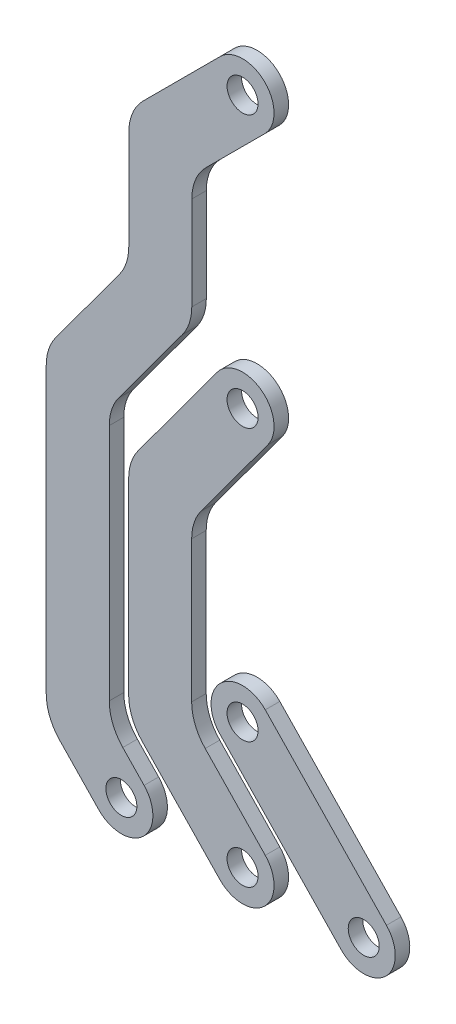
SolidWorks part; units mm, degrees
ref_plane "前视基准面" through (0, 0, 0) normal (0, 0, 1) x (1, 0, 0)
ref_plane "上视基准面" through (0, 0, 0) normal (0, 1, 0) x (1, 0, 0)
ref_plane "右视基准面" through (0, 0, 0) normal (1, 0, 0) x (0, 0, -1)
sketch "草图1"
  dimension "D1" = 26
  dimension "D2" = 0
sketch_block_instance "块1-1"
sketch_block "块1"
sketch_block_instance "块2-1"
sketch_block "块2"
sketch "草图2" plane through (0, 0, 0) normal (0, 0, 1) x (1, 0, 0)
  circle A0 centre (-5.5865, -343.2) radius 6.5
  circle A1 centre (-5.5865, -287.2) radius 6
  circle A2 centre (-5.5865, -287.2) radius 6
  circle A3 centre (-5.5865, -343.2) radius 6
  circle A4 centre (-5.5865, -343.2) radius 6
  circle A5 centre (-5.5865, -231.2) radius 6
  circle A6 centre (-5.5865, -231.2) radius 6
  circle A7 centre (-30.5865, -369.2) radius 2.5
  circle A8 centre (-30.5865, -369.2) radius 2.5
  circle A9 centre (-5.5865, -369.2) radius 2.5
  circle A10 centre (-5.5865, -369.2) radius 2.5
  circle A11 centre (19.4135, -369.2) radius 2.5
  circle A12 centre (19.4135, -369.2) radius 2.5
  circle A13 centre (-5.5865, -287.2) radius 6.5
  circle A14 centre (-5.5865, -231.2) radius 6.5
  circle A15 centre (-5.5865, -369.2) radius 6.5
  circle A16 centre (19.4135, -369.2) radius 6.5
  circle A17 centre (-30.5865, -369.2) radius 6.5
  dimension "D4" = 13
  dimension "D8" = 13
  dimension "D9" = 13
  dimension "D1" = 0
  dimension "D2" = 0
  dimension "D3" = 0
  dimension "D5" = 0
  dimension "D6" = 0
  dimension "D7" = 0
  dimension "D10" = 0.5
sketch "草图3" plane through (0, 0, 0) normal (0, 0, 1) x (1, 0, 0)
  line L26 (-5.5865, -287.2) -> (-22.5865, -310.3173)
  line L27 (-22.5865, -310.3173) -> (-22.5865, -351.52)
  line L28 (-22.5865, -351.52) -> (-5.5865, -369.2)
  line L29 (-39.5865, -298.5954) -> (-5.5865, -252.3607)
  line L30 (-39.5865, -298.5954) -> (-39.5865, -359.84)
  line L31 (-39.5865, -359.84) -> (-30.5865, -369.2)
  line L32 (-5.5865, -343.2) -> (19.4135, -369.2)
  line L33 (-10.2719, -347.7052) -> (14.7281, -373.7052)
  line L34 (-0.9011, -338.6948) -> (24.0989, -364.6948)
  line L35 (-5.5865, -252.3607) -> (-5.5865, -231.2)
  line L36 (-10.8231, -283.3492) -> (-29.0865, -308.1846)
  line L37 (-29.0865, -308.1846) -> (-29.0865, -354.138)
  line L38 (-29.0865, -354.138) -> (-10.2719, -373.7052)
  line L39 (-33.0865, -357.222) -> (-25.9011, -364.6948)
  line L40 (-33.0865, -300.7281) -> (-33.0865, -357.222)
  line L41 (-33.0865, -300.7281) -> (0.9135, -254.4934)
  line L42 (0.9135, -254.4934) -> (0.9135, -231.2)
  line L43 (-0.35, -291.0508) -> (-16.0865, -312.45)
  line L44 (-16.0865, -312.45) -> (-16.0865, -348.902)
  line L45 (-16.0865, -348.902) -> (-0.9011, -364.6948)
  line L46 (-46.0865, -362.458) -> (-35.2719, -373.7052)
  line L47 (-46.0865, -296.4627) -> (-46.0865, -362.458)
  line L48 (-46.0865, -296.4627) -> (-12.0865, -250.228)
  line L49 (-12.0865, -250.228) -> (-12.0865, -231.2)
  circle A13 centre (-5.5865, -343.2) radius 6.5
  circle A14 centre (-5.5865, -343.2) radius 6.5
  circle A15 centre (-30.5865, -369.2) radius 6.5
  circle A16 centre (-30.5865, -369.2) radius 6.5
  circle A17 centre (19.4135, -369.2) radius 6.5
  circle A18 centre (19.4135, -369.2) radius 6.5
  circle A19 centre (-5.5865, -369.2) radius 6.5
  circle A20 centre (-5.5865, -369.2) radius 6.5
  circle A21 centre (-5.5865, -231.2) radius 6.5
  circle A22 centre (-5.5865, -231.2) radius 6.5
  circle A23 centre (-5.5865, -287.2) radius 6.5
  circle A24 centre (-5.5865, -287.2) radius 6.5
  dimension "D2" = 6.5
  dimension "D3" = 6.5
  dimension "D4" = 6.5
  dimension "D5" = 6.5
  dimension "D6" = 7.64
  dimension "D7" = 4
  dimension "D9" = 4
  dimension "D10" = 143.67
  dimension "D8" = 0
  dimension "D11" = 0
  dimension "D12" = 0
  dimension "D13" = 0
  dimension "D14" = 0
  dimension "D15" = 0
sketch "草图4" plane through (0, 0, 0) normal (0, 0, 1) x (1, 0, 0)
  line L3 (-33.0865, -357.222) -> (-25.9011, -364.6948) construction
  line L10 (-33.0865, -300.7281) -> (-33.0865, -357.222) construction
  line L36 (-33.0865, -300.7281) -> (0.9135, -254.4934) construction
  line L37 (0.9135, -254.4934) -> (0.9135, -231.2) construction
  line L38 (-10.8231, -283.3492) -> (-29.0865, -308.1846) construction
  line L39 (-29.0865, -308.1846) -> (-29.0865, -354.138) construction
  line L40 (-29.0865, -354.138) -> (-10.2719, -373.7052) construction
  line L41 (-0.9011, -338.6948) -> (24.0989, -364.6948) construction
  line L42 (-10.2719, -347.7052) -> (14.7281, -373.7052) construction
  line L43 (-46.0865, -362.458) -> (-35.2719, -373.7052) construction
  line L44 (-46.0865, -296.4627) -> (-46.0865, -362.458) construction
  line L45 (-46.0865, -296.4627) -> (-12.0865, -250.228) construction
  line L46 (-12.0865, -250.228) -> (-12.0865, -231.2) construction
  line L47 (-0.35, -291.0508) -> (-16.0865, -312.45) construction
  line L48 (-16.0865, -312.45) -> (-16.0865, -348.902) construction
  line L49 (-16.0865, -348.902) -> (-0.9011, -364.6948) construction
  line L58 (-33.0865, -357.222) -> (-25.9011, -364.6948)
  line L59 (-33.0865, -300.7281) -> (-33.0865, -357.222)
  line L60 (-33.0865, -300.7281) -> (0.9135, -254.4934)
  line L61 (0.9135, -254.4934) -> (0.9135, -231.2)
  line L62 (-10.8231, -283.3492) -> (-29.0865, -308.1846)
  line L63 (-29.0865, -308.1846) -> (-29.0865, -354.138)
  line L64 (-29.0865, -354.138) -> (-10.2719, -373.7052)
  line L65 (-0.9011, -338.6948) -> (24.0989, -364.6948)
  line L66 (-10.2719, -347.7052) -> (14.7281, -373.7052)
  line L67 (-46.0865, -362.458) -> (-35.2719, -373.7052)
  line L68 (-46.0865, -296.4627) -> (-46.0865, -362.458)
  line L69 (-46.0865, -296.4627) -> (-12.0865, -250.228)
  line L70 (-12.0865, -250.228) -> (-12.0865, -231.2)
  line L71 (-0.35, -291.0508) -> (-16.0865, -312.45)
  line L72 (-16.0865, -312.45) -> (-16.0865, -348.902)
  line L73 (-16.0865, -348.902) -> (-0.9011, -364.6948)
  circle A1 centre (-5.5865, -343.2) radius 6.5
  arc A3 (-0.9011, -338.6948) -> (-10.2719, -347.7052) centre (-5.5865, -343.2) ccw
  circle A5 centre (-5.5865, -231.2) radius 6.5
  arc A7 (0.9135, -231.2) -> (-12.0865, -231.2) centre (-5.5865, -231.2) ccw
  circle A9 centre (-5.5865, -369.2) radius 6.5
  arc A11 (-10.2719, -373.7052) -> (-0.9011, -364.6948) centre (-5.5865, -369.2) ccw
  circle A13 centre (19.4135, -369.2) radius 6.5
  arc A14 (14.7281, -373.7052) -> (24.0989, -364.6948) centre (19.4135, -369.2) ccw
  circle A15 centre (-30.5865, -369.2) radius 6.5
  arc A16 (-35.2719, -373.7052) -> (-25.9011, -364.6948) centre (-30.5865, -369.2) ccw
  circle A17 centre (-5.5865, -287.2) radius 6.5
  arc A18 (-0.35, -291.0508) -> (-10.8231, -283.3492) centre (-5.5865, -287.2) ccw
  dimension "D1" = 0
  dimension "D2" = 0
  dimension "D3" = 0
  dimension "D4" = 0
  dimension "D5" = 0
  dimension "D6" = 0
extrude "凸台-拉伸1" add sketch "草图4" along normal blind 3
hole_wizard "M6 间隙孔1" positions "草图5" profile "草图6" hole size "M6" standard "GB" end condition through all
sketch "草图5" plane through (0, 0, 0) normal (0, 0, -1) x (-1, 0, 0)
  point P0 (-19.4135, -369.2)
  point P3 (5.5865, -369.2)
  point P6 (30.5865, -369.2)
  point P9 (5.5865, -287.2)
  point P12 (5.5865, -343.2)
  point P15 (5.5865, -231.2)
sketch "草图6" plane through (19.4135, -369.2, 0) normal (1, 0, 0) x (0, 1, 0)
  line L0 (0, 0) -> (0, 3)
  line L1 (0, 3) -> (3.2, 3)
  line L2 (3.2, 3) -> (3.2, 0)
  line L5 (3.2, 0) -> (0, 0)
  line L11 (0, -6.35) -> (0, 107.95) construction
  dimension "通孔孔直径" = 6.4
  dimension "通孔孔深度" = 3
fillet "圆角1" radius 10 4 edges at (-16.0865, -312.45, 1.5) (-16.0865, -348.902, 1.5) (-29.0865, -354.138, 1.5) (-29.0865, -308.1846, 1.5)
fillet "圆角2" radius 10 6 edges at (-33.0865, -357.222, 1.5) (-46.0865, -362.458, 1.5) (-46.0865, -296.4627, 1.5) (-33.0865, -300.7281, 1.5) (0.9135, -254.4934, 1.5) (-12.0865, -250.228, 1.5)
sketch "草图7" plane through (0, 0, 0) normal (0, 0, -1) x (-1, 0, 0)
  line L0 (16.0617, -277.5769) -> (16.0617, -250.8675)
  line L2 (16.0617, -250.8675) -> (0.9903, -235.7962)
  line L3 (10.1827, -226.6038) -> (29.0617, -245.4827)
  line L4 (29.0617, -245.4827) -> (29.0617, -295.2549)
  line L15 (-0.9135, -231.2) -> (-0.9135, -251.2124)
  line L16 (1.0304, -257.1367) -> (31.1427, -298.0848)
  line L17 (33.0865, -304.0091) -> (33.0865, -353.1942)
  line L18 (30.2949, -360.1253) -> (25.9011, -364.6948)
  line L19 (35.2719, -373.7052) -> (43.2949, -365.3614)
  line L20 (46.0865, -358.4303) -> (46.0865, -299.7437)
  line L21 (44.1427, -293.8194) -> (14.0304, -252.8713)
  line L22 (12.0865, -246.947) -> (12.0865, -231.2)
  line L23 (-0.9135, -231.2) -> (-0.9135, -251.2124)
  line L24 (1.0304, -257.1367) -> (31.1427, -298.0848)
  line L25 (33.0865, -304.0091) -> (33.0865, -353.1942)
  line L26 (30.2949, -360.1253) -> (25.9011, -364.6948)
  line L27 (35.2719, -373.7052) -> (43.2949, -365.3614)
  line L28 (46.0865, -358.4303) -> (46.0865, -299.7437)
  line L29 (44.1427, -293.8194) -> (14.0304, -252.8713)
  line L30 (12.0865, -246.947) -> (12.0865, -231.2)
  circle A0 centre (5.5865, -231.2) radius 3.2
  circle A1 centre (5.5865, -231.2) radius 6.5
  arc A10 (-0.9135, -251.2124) -> (1.0304, -257.1367) centre (9.0865, -251.2124) ccw
  arc A11 (33.0865, -304.0091) -> (31.1427, -298.0848) centre (23.0865, -304.0091) ccw
  arc A12 (30.2949, -360.1253) -> (33.0865, -353.1942) centre (23.0865, -353.1942) ccw
  arc A13 (25.9011, -364.6948) -> (35.2719, -373.7052) centre (30.5865, -369.2) ccw
  arc A14 (43.2949, -365.3614) -> (46.0865, -358.4303) centre (36.0865, -358.4303) ccw
  arc A15 (46.0865, -299.7437) -> (44.1427, -293.8194) centre (36.0865, -299.7437) ccw
  arc A16 (12.0865, -246.947) -> (14.0304, -252.8713) centre (22.0865, -246.947) ccw
  arc A17 (12.0865, -231.2) -> (-0.9135, -231.2) centre (5.5865, -231.2) ccw
  arc A18 (-0.9135, -251.2124) -> (1.0304, -257.1367) centre (9.0865, -251.2124) ccw
  arc A19 (33.0865, -304.0091) -> (31.1427, -298.0848) centre (23.0865, -304.0091) ccw
  arc A20 (30.2949, -360.1253) -> (33.0865, -353.1942) centre (23.0865, -353.1942) ccw
  arc A21 (25.9011, -364.6948) -> (35.2719, -373.7052) centre (30.5865, -369.2) ccw
  arc A22 (43.2949, -365.3614) -> (46.0865, -358.4303) centre (36.0865, -358.4303) ccw
  arc A23 (46.0865, -299.7437) -> (44.1427, -293.8194) centre (36.0865, -299.7437) ccw
  arc A24 (12.0865, -246.947) -> (14.0304, -252.8713) centre (22.0865, -246.947) ccw
  arc A25 (12.0865, -231.2) -> (-0.9135, -231.2) centre (5.5865, -231.2) ccw
  circle M2 centre (5.5865, -231.2) radius 3.2
  line M3 (-0.9135, -231.2) -> (-0.9135, -251.2124)
  arc M4 (-0.9135, -251.2124) -> (1.0304, -257.1367) centre (9.0865, -251.2124) ccw
  line M5 (1.0304, -257.1367) -> (31.1427, -298.0848)
  line M15 (44.1427, -293.8194) -> (14.0304, -252.8713)
  arc M16 (14.0304, -252.8713) -> (12.0865, -246.947) centre (22.0865, -246.947) cw
  line M17 (12.0865, -246.947) -> (12.0865, -231.2)
  arc M18 (12.0865, -231.2) -> (-0.9135, -231.2) centre (5.5865, -231.2) ccw
  dimension "D1" = 135
  dimension "D2" = 13
  dimension "D3" = 0
extrude "切除-拉伸1" cut sketch "草图7" against normal blind 10 contours A1 L0 L2 M3 M4 M5 M15 M16 M17 | A1 L2 M17 | A1 M18 M2 region at (-7.6962, -254.727, 0) region at (-9.1985, -239.92, 0) region at (-3.1694, -225.3646, 0)
extrude "凸台-拉伸2" add sketch "草图7<3>" against normal up to surface (3 mm away) contours L4 L3 L2 L0 M18 M17 M15 | A1 L2 M17 | A1 M18 M2 region at (-21.1696, -249.697, 0) region at (-9.1985, -239.92, 0) region at (-3.1694, -225.3646, 0) up to face at (-33.1919, -325.7745, 3)
sketch "草图7<3>" plane through (0, 0, 0) normal (0, 0, -1) x (-1, 0, 0) same geometry as "草图7"
fillet "圆角3" radius 10 4 edges at (-16.0617, -277.5769, 1.5) (-16.0617, -250.8675, 1.5) (-29.0617, -245.4827, 1.5) (-29.0617, -273.3115, 1.5)
